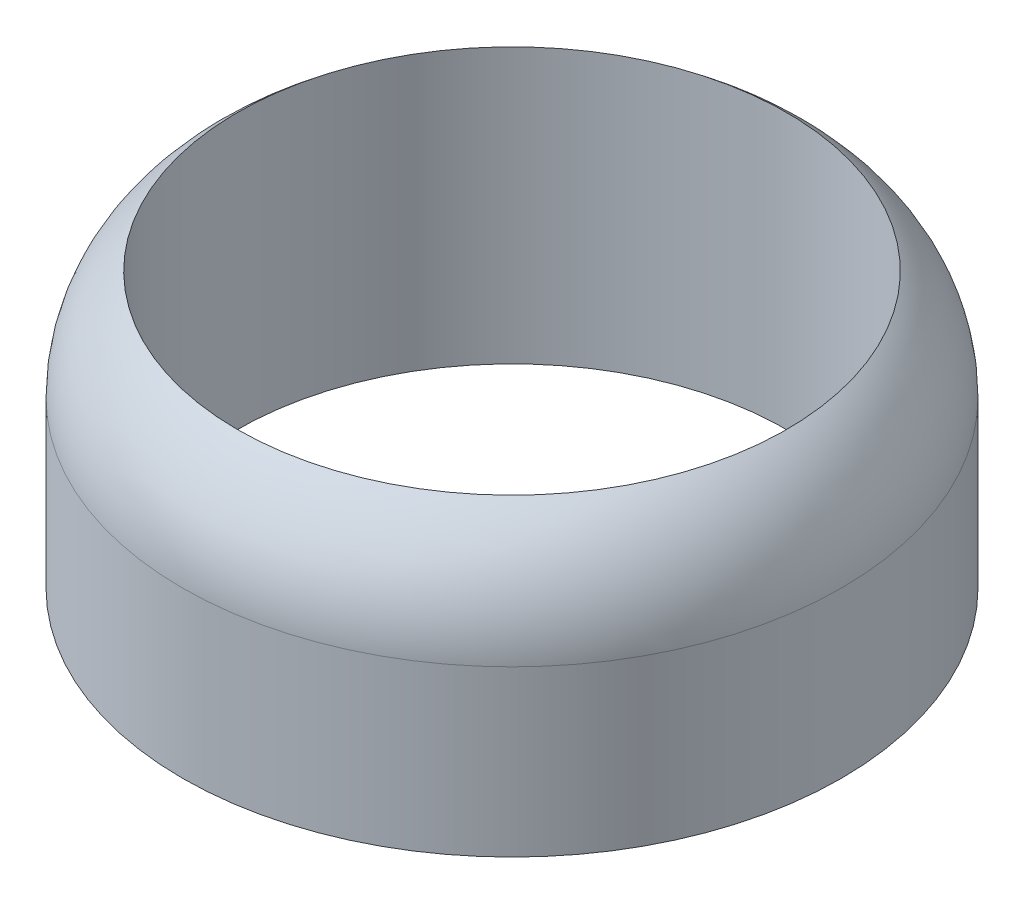
SolidWorks part; units mm, degrees
ref_plane "Front Plane" through (0, 0, 0) normal (0, 0, 1) x (1, 0, 0)
ref_plane "Top Plane" through (0, 0, 0) normal (0, 1, 0) x (1, 0, 0)
ref_plane "Right Plane" through (0, 0, 0) normal (1, 0, 0) x (0, 0, -1)
sketch "Sketch1" plane through (0, 0, 0) normal (0, 1, 0) x (1, 0, 0)
  circle A0 centre (0, 0) radius 10
  circle A1 centre (0, 0) radius 12
  dimension "D1" = 20
  dimension "D2" = 2
extrude "Boss-Extrude1" add sketch "Sketch1" along normal blind 10
fillet "Fillet1" radius 5 1 edges at (0, 10, 12)
